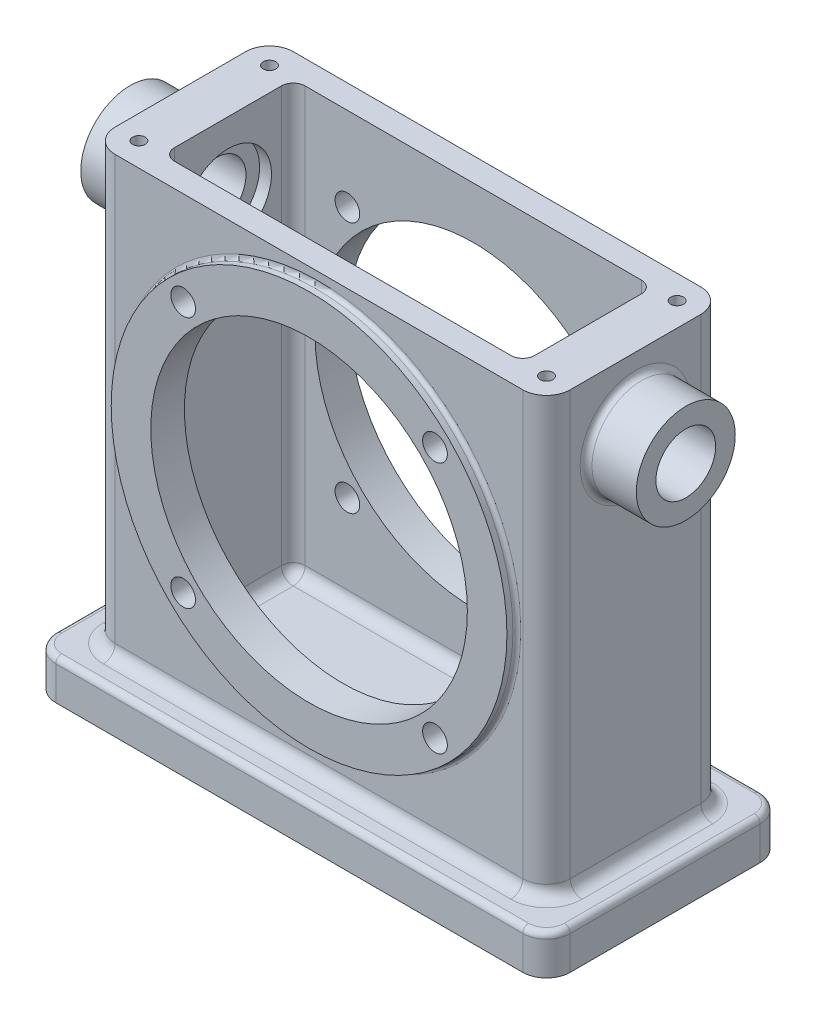
SolidWorks part; units mm, degrees
note: '?' marks a value the reader was unsure of.
ref_plane "Front" through (0, 0, 0) normal (0, 0, 1) x (1, 0, 0)
ref_plane "Top" through (0, 0, 0) normal (0, 1, 0) x (1, 0, 0)
ref_plane "Right" through (0, 0, 0) normal (1, 0, 0) x (0, 0, -1)
other "Configuration Table"
sketch "Sketch1" plane through (0, 0, 0) normal (0, 1, 0) x (1, 0, 0)
  line L0 (-65, -30) -> (65, 30) construction
  line L1 (-65, -30) -> (65, -30)
  line L2 (-65, -30) -> (-65, 30)
  line L3 (-65, 30) -> (65, 30)
  line L4 (65, -30) -> (65, 30)
  dimension "D1" = 130
  dimension "D2" = 60
extrude "Base-Extrude" add sketch "Sketch1" along normal blind 10
sketch "Sketch2" plane through (0, 10, 0) normal (0, 1, 0) x (-1, 0, 0)
  line L0 (57.5, 22.5) -> (-57.5, -22.5) construction
  line L1 (57.5, 22.5) -> (-57.5, 22.5)
  line L2 (57.5, 22.5) -> (57.5, -22.5)
  line L3 (57.5, -22.5) -> (-57.5, -22.5)
  line L4 (-57.5, 22.5) -> (-57.5, -22.5)
  dimension "D1" = 115
  dimension "D2" = 45
extrude "Boss-Extrude1" add sketch "Sketch2" along normal blind 110
fillet "Fillet1" radius 6 8 edges at (-57.5, 65, -22.5) (-57.5, 65, 22.5) (57.5, 65, 22.5) (57.5, 65, -22.5) (-65, 5, -30) (65, 5, -30) (65, 5, 30) (-65, 5, 30)
fillet "Fillet2" radius 1.5 8 edges at (0, 10, 30) (-65, 10, 0) (65, 10, 0) (0, 10, -30) (-63.2426, 10, -28.2426) (63.2426, 10, 28.2426) (63.2426, 10, -28.2426) (-63.2426, 10, 28.2426)
fillet "Fillet3" radius 3 8 edges at (-57.5, 10, 0) (0, 10, -22.5) (57.5, 10, 0) (0, 10, 22.5) (-55.7426, 10, 20.7426) (-55.7426, 10, -20.7426) (55.7426, 10, 20.7426) (55.7426, 10, -20.7426)
sketch "Sketch3" plane through (0, 120, 0) normal (0, 1, 0) x (-1, 0, 0)
  line L2 (51.5, 16.5) -> (-51.5, 16.5)
  line L3 (42.5, 16.5) -> (-42.5, 16.5)
  line L5 (-51.5, -16.5) -> (51.5, -16.5)
  line L6 (-42.5, -16.5) -> (42.5, -16.5)
  line L8 (45.5, -16.5) -> (45.5, 16.5)
  line L9 (45.5, -13.5) -> (45.5, 13.5)
  line L11 (-45.5, 16.5) -> (-45.5, -16.5)
  line L12 (-45.5, 13.5) -> (-45.5, -13.5)
  arc A0 (-42.5, 16.5) -> (-45.5, 13.5) centre (-42.5, 13.5) ccw
  arc A1 (45.5, 13.5) -> (42.5, 16.5) centre (42.5, 13.5) ccw
  arc A2 (42.5, -16.5) -> (45.5, -13.5) centre (42.5, -13.5) ccw
  arc A3 (-45.5, -13.5) -> (-42.5, -16.5) centre (-42.5, -13.5) ccw
  dimension "D5" = 3
  dimension "D1" = 6
  dimension "D2" = 6
  dimension "D3" = 12
  dimension "D4" = 12
extrude "Cut-Extrude1" cut sketch "Sketch3" against normal blind 107.95
fillet "Fillet4" radius 3 8 edges at (44.6213, 12.05, 15.6213) (0, 12.05, 16.5) (-44.6213, 12.05, 15.6213) (-45.5, 12.05, 0) (-44.6213, 12.05, -15.6213) (0, 12.05, -16.5) (44.6213, 12.05, -15.6213) (45.5, 12.05, 0)
sketch "Sketch4" plane through (0, 0, 22.5) normal (0, 0, 1) x (1, 0, 0)
  line L0 (-51.5, 120) -> (51.5, 120) construction
  line L1 (0, -50) -> (0, 50) construction
  circle A0 centre (0, 67) radius 50
  dimension "D1" = 100
  dimension "D2" = 53
extrude "Boss-Extrude2" add sketch "Sketch4" along normal blind 2.5
mirror "Mirror1" about plane through (0, 0, 0) normal (0, 0, 1) of "Boss-Extrude2"
sketch "Sketch5" plane through (0, 0, 25) normal (0, 0, 1) x (1, 0, 0)
  circle A0 centre (0, 67) radius 40
  dimension "D1" = 80
extrude "Cut-Extrude2" cut sketch "Sketch5" against normal through all
fillet "Fillet5" radius 1 2 edges at (-50, 67, 22.5) (50, 67, -22.5)
sketch "Sketch6" plane through (57.5, 0, 0) normal (1, 0, 0) x (0, 0, -1)
  line L0 (-24, 0) -> (24, 0) construction
  line L1 (0, 102) -> (0, 0) construction
  circle A0 centre (0, 102) radius 12.5
  dimension "D1" = 25
  dimension "D2" = 102
extrude "Boss-Extrude3" add sketch "Sketch6" along normal blind 12.7
sketch "Sketch7" plane through (45.5, 0, 0) normal (-1, 0, 0) x (0, 0, 1)
  circle A0 centre (0, 102) radius 7.55
  dimension "D1" = 15.1
extrude "Cut-Extrude3" cut sketch "Sketch7" against normal through all
sketch "Sketch8" plane through (45.5, 0, 0) normal (-1, 0, 0) x (0, 0, 1)
  circle A0 centre (0, 102) radius 11
  dimension "D1" = 22
extrude "Cut-Extrude4" cut sketch "Sketch8" against normal blind 3
mirror "Mirror3" about plane through (0, 0, 0) normal (1, 0, 0) of "Cut-Extrude4", "Cut-Extrude3", "Boss-Extrude3"
fillet "Fillet6" radius 1.5 2 edges at (57.5, 102, 12.5) (-57.5, 102, -12.5)
sketch "Sketch9" plane through (0, 0, 25) normal (0, 0, 1) x (1, 0, 0)
  line L0 (31.8198, 98.8198) -> (0, 67) construction
  line L1 (0, 67) -> (45, 67) construction
  circle A0 centre (0, 67) radius 45 construction
  circle A1 centre (31.8198, 98.8198) radius 3.125
  dimension "D1" = 90
  dimension "D2" = 6.25
  dimension "D3" = 45
extrude "Cut-Extrude5" cut sketch "Sketch9" against normal through all
ref_axis "CenterLargeHole" through (0, 67, -82.4461) along (0, 0, 1)?
pattern_circular "CirPattern1" count 4 over 360 about axis through (0, 67, 0) along (0, 0, 1) of "Cut-Extrude5"
sketch "Sketch10" plane through (0, 120, 0) normal (0, 1, 0) x (-1, 0, 0)
  line L0 (-42.5, -16.5) -> (42.5, -16.5) construction
  line L1 (42.5, 16.5) -> (-42.5, 16.5) construction
  line L2 (-57.5, 16.5) -> (-57.5, -16.5) construction
  circle A0 centre (-51.5, -16.5) radius 1.6
  circle A1 centre (-51.5, 16.5) radius 1.6
  dimension "D1" = 3.2
  dimension "D2" = 6
extrude "Cut-Extrude6" cut sketch "Sketch10" against normal blind 19.05
mirror "Mirror4" about plane through (0, 0, 0) normal (1, 0, 0) of "Cut-Extrude6"
